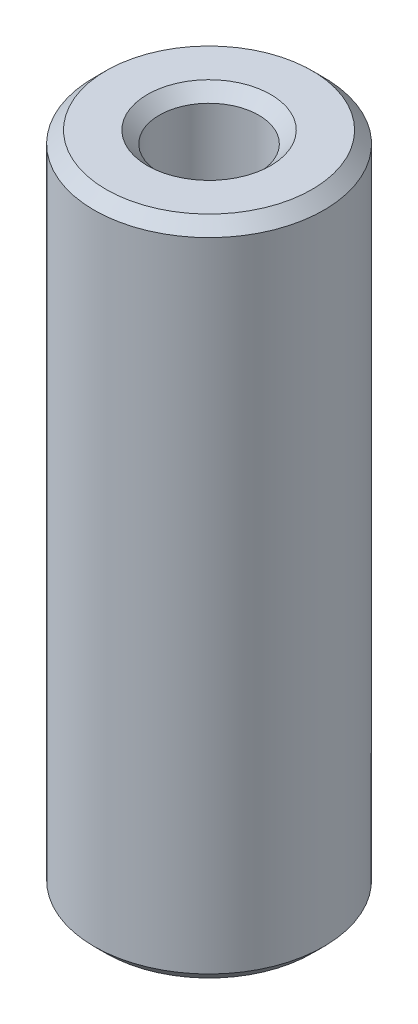
SolidWorks part; units mm, degrees
ref_plane "Front Plane" through (0, 0, 0) normal (0, 0, 1) x (1, 0, 0)
ref_plane "Top Plane" through (0, 0, 0) normal (0, 1, 0) x (1, 0, 0)
ref_plane "Right Plane" through (0, 0, 0) normal (1, 0, 0) x (0, 0, -1)
sketch "Sketch1" plane through (0, 0, 0) normal (0, 1, 0) x (1, 0, 0)
  circle A0 centre (0, 0) radius 22.5
  dimension "SLEEVE_OD" = 45
extrude "Boss-Extrude1" add sketch "Sketch1" along normal blind 129.5708
sketch "Sketch2" plane through (0, 0, 0) normal (0, 1, 0) x (1, 0, 0)
  circle A0 centre (0, 0) radius 9.7397
  dimension "BORE_D" = 19.4795
extrude "Cut-Extrude1" cut sketch "Sketch2" along normal through all
chamfer "Chamfer1" distance 2.3397 angle 45 4 edges at (0, 129.5708, 9.7397) (0, 0, 9.7397) (0, 0, 22.5) (0, 129.5708, 22.5)
